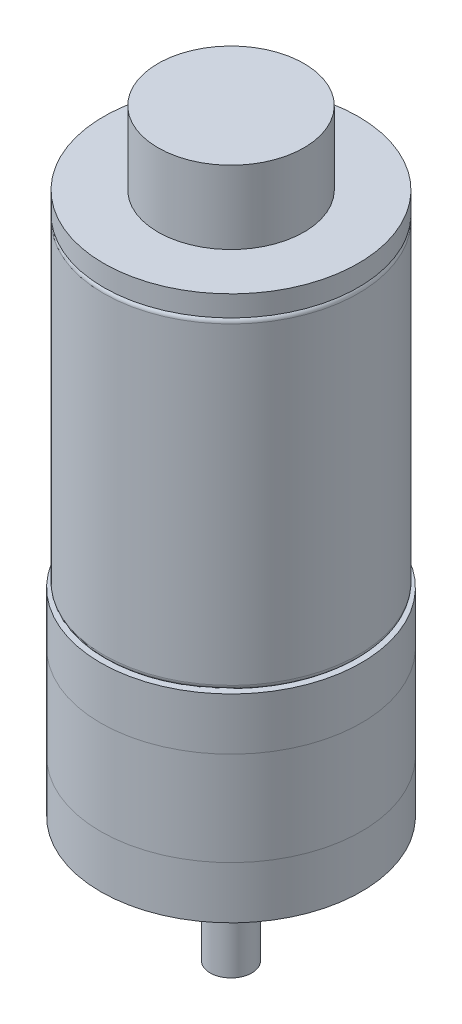
SolidWorks part; units mm, degrees
ref_plane "Front Plane" through (0, 0, 0) normal (0, 0, 1) x (1, 0, 0)
ref_plane "Top Plane" through (0, 0, 0) normal (0, 1, 0) x (1, 0, 0)
ref_plane "Right Plane" through (0, 0, 0) normal (1, 0, 0) x (0, 0, -1)
sketch "Sketch1" plane through (0, 0, 0) normal (0, 1, 0) x (1, 0, 0)
  circle A0 centre (0, 0) radius 12.2
  dimension "D1" = 24.4
extrude "Boss-Extrude1" add sketch "Sketch1" along normal blind 31
sketch "Sketch2" plane through (0, 31, 0) normal (0, 1, 0) x (1, 0, 0)
  circle A0 centre (0, 0) radius 12.2
  dimension "D1" = 24.4
extrude "Boss-Extrude2" add sketch "Sketch2" along normal blind 2 separate body
sketch "Sketch3" plane through (0, 33, 0) normal (0, 1, 0) x (1, 0, 0)
  circle A0 centre (0, 0) radius 7
  dimension "D1" = 14
extrude "Boss-Extrude3" add sketch "Sketch3" along normal blind 7 separate body contours A0
sketch "Sketch4" plane through (0, 0, 0) normal (0, -1, 0) x (1, 0, 0)
  circle A0 centre (0, 0) radius 12.5
  dimension "D1" = 25
extrude "Boss-Extrude5" add sketch "Sketch4" along normal blind 5 separate body
sketch "Sketch5" plane through (0, -5, 0) normal (0, -1, 0) x (1, 0, 0)
  circle A0 centre (0, 0) radius 12.5
  dimension "D1" = 25
extrude "Boss-Extrude6" add sketch "Sketch5" along normal blind 9 separate body
sketch "Sketch6" plane through (0, -14, 0) normal (0, -1, 0) x (1, 0, 0)
  circle A0 centre (0, 0) radius 12.5
  dimension "D1" = 25
extrude "Boss-Extrude7" add sketch "Sketch6" along normal blind 5 separate body
sketch "Sketch7" plane through (0, -19, 0) normal (0, -1, 0) x (1, 0, 0)
  circle A0 centre (0, 0) radius 3.5
  dimension "D1" = 7
extrude "Boss-Extrude8" add sketch "Sketch7" along normal blind 2.5
sketch "Sketch8" plane through (0, -21.5, 0) normal (0, -1, 0) x (1, 0, 0)
  circle A0 centre (0, 0) radius 2
  dimension "D1" = 4
extrude "Boss-Extrude9" add sketch "Sketch8" along normal blind 9.5 separate body
sketch "Sketch9" plane through (0, -19, 0) normal (0, -1, 0) x (1, 0, 0)
  line L0 (0, 0) -> (0, 12.5) construction
  line L1 (0, 0) -> (0, -12.5) construction
  circle A0 centre (0, 0) radius 12.5 construction
  circle A1 centre (0, -8) radius 1.5
  circle A2 centre (0, 8) radius 1.5
  dimension "D1" = 3
  dimension "D2" = 3
  dimension "D3" = 16
  dimension "D4" = 8
extrude "Cut-Extrude1" cut sketch "Sketch9" against normal blind 5 contours A2 | A1
thread "Thread1" pitch 0.3175 method extrude profile "Thread Profile2" start angle 0, offset 0, length 5, pitch 0.3175, diameter 3
ref_plane "Plane2" through (1.5, -19, -8) normal (0, 0, 1) x (1, 0, 0)
sketch "Thread Profile2" plane through (1.5, -19, -8) normal (0, 0, 1) x (1, 0, 0)
  line L0 (0, 0) -> (0, 0.3175) construction
  line L11 (0, 0) -> (0, 0.2778)
  line L12 (0, 0.2778) -> (-0.1719, 0.1786)
  line L13 (-0.1719, 0.1786) -> (-0.1719, 0.0992)
  line L15 (-0.1719, 0.0992) -> (0, 0)
  line L17 (-0.1719, 0.1389) -> (0, 0.1389) construction
  point P2 (0, 0)
  dimension "Pitch" = 0.3175
  dimension "Profile_Angle" = 60
  dimension "Profile_Land" = 0.0794
  dimension "Profile_Height" = 0.1719
thread "Thread2" pitch 0.3175 method extrude profile "Thread Profile3" start angle 0, offset 0, length 5, pitch 0.3175, diameter 3
ref_plane "Plane3" through (1.5, -19, 8) normal (0, 0, 1) x (1, 0, 0)
sketch "Thread Profile3" plane through (1.5, -19, 8) normal (0, 0, 1) x (1, 0, 0)
  line L0 (0, 0) -> (0, 0.3175) construction
  line L11 (0, 0) -> (0, 0.2778)
  line L12 (0, 0.2778) -> (-0.1719, 0.1786)
  line L13 (-0.1719, 0.1786) -> (-0.1719, 0.0992)
  line L15 (-0.1719, 0.0992) -> (0, 0)
  line L17 (-0.1719, 0.1389) -> (0, 0.1389) construction
  point P2 (0, 0)
  dimension "Pitch" = 0.3175
  dimension "Profile_Angle" = 60
  dimension "Profile_Land" = 0.0794
  dimension "Profile_Height" = 0.1719
fillet "Fillet2" radius 0.5 2 edges at (0, 0, 12.2) (0, 31, 12.2)
